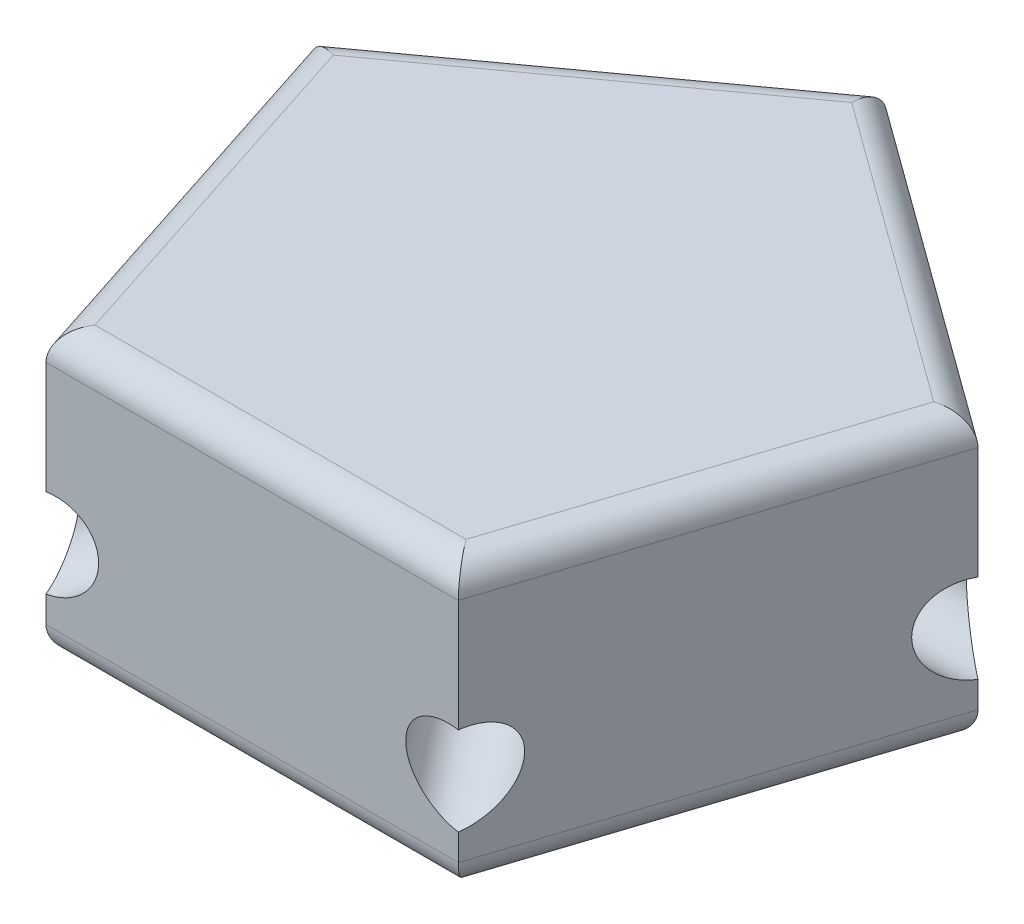
SolidWorks part; units mm, degrees
ref_plane "Front Plane" through (0, 0, 0) normal (0, 0, 1) x (1, 0, 0)
ref_plane "Top Plane" through (0, 0, 0) normal (0, 1, 0) x (1, 0, 0)
ref_plane "Right Plane" through (0, 0, 0) normal (1, 0, 0) x (0, 0, -1)
sketch "Sketch1" plane through (0, 0, 0) normal (0, 1, 0) x (1, 0, 0)
  line L1 (-7.2654, -10) -> (7.2654, -10)
  line L2 (7.2654, -10) -> (11.7557, 3.8197)
  line L3 (11.7557, 3.8197) -> (0, 12.3607)
  line L4 (0, 12.3607) -> (-11.7557, 3.8197)
  line L5 (-11.7557, 3.8197) -> (-7.2654, -10)
  circle A0 centre (0, 0) radius 10 construction
  dimension "D1" = 20
extrude "Boss-Extrude1" add sketch "Sketch1" along normal blind 3 and the other way blind 7
ref_axis "Axis1" through (0, 5.5, 0) along (0, -1, 0)
fillet "Fillet1" radius 1 10 edges at (0, -7, 10) (9.5106, -7, 3.0902) (5.8779, -7, -8.0902) (-5.8779, -7, -8.0902) (-9.5106, -7, 3.0902) (-5.8779, 3, -8.0902) (5.8779, 3, -8.0902) (9.5106, 3, 3.0902) (0, 3, 10) (-9.5106, 3, 3.0902)
ref_plane "Plane1" through (-2.2617, -1.0931, 3.1129) normal (0.5654, 0.2733, -0.7782) x (-0.8248, 0.1873, -0.5335)
sketch "Sketch2" plane through (-2.2617, -1.0931, 3.1129) normal (0.5654, 0.2733, -0.7782) x (-0.8248, 0.1873, -0.5335)
  circle A0 centre (0, 0) radius 1.5 construction
  circle A1 centre (0, 0) radius 1.5
extrude "Cut-Extrude1" cut sketch "Sketch2" against normal through all
pattern_circular "CirPattern1" count 5 over 360 about axis through (0, 5.5, 0) along (0, -1, 0) of "Cut-Extrude1"
